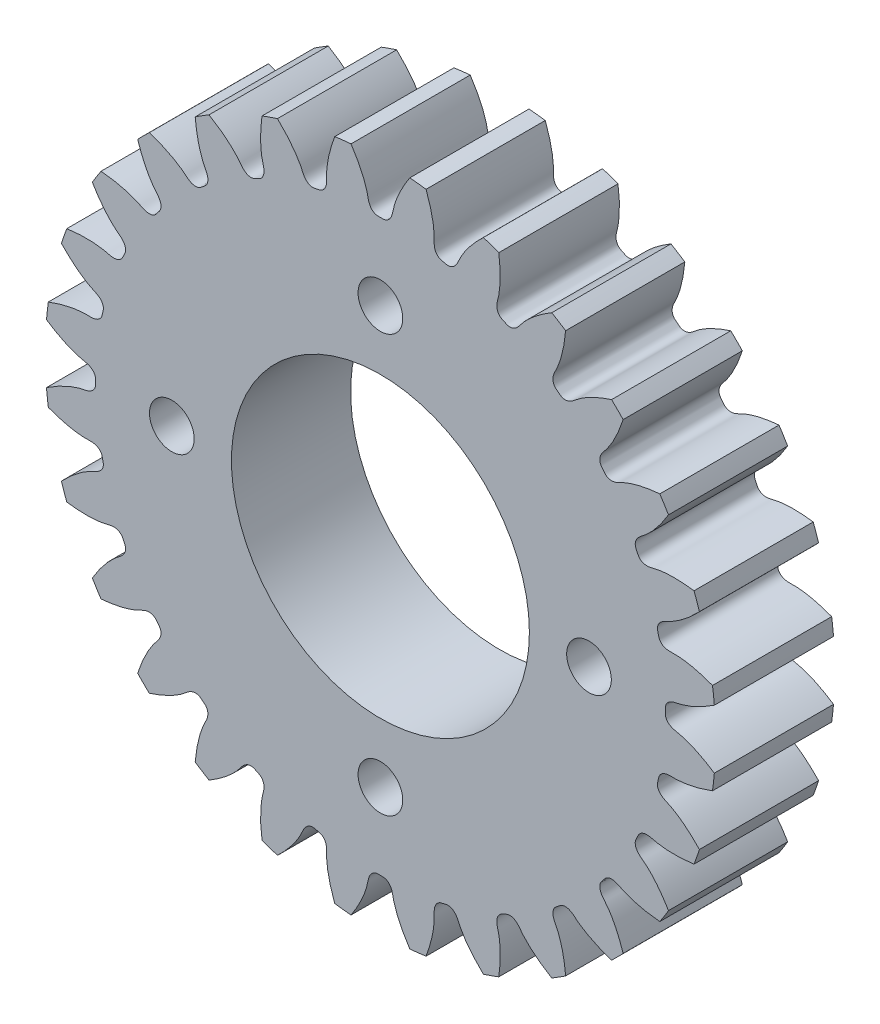
SolidWorks part; units mm, degrees
ref_plane "Front Plane" through (0, 0, 0) normal (0, 0, 1) x (1, 0, 0)
ref_plane "Top Plane" through (0, 0, 0) normal (0, 1, 0) x (1, 0, 0)
ref_plane "Right Plane" through (0, 0, 0) normal (1, 0, 0) x (0, 0, -1)
ref_axis "Axis1" through (0, 0, 4.4) along (0, 0, -1)
sketch "SketchRevolveSpurAssembly01Gear" plane through (0, 0, 0) normal (1, 0, 0) x (0, 0, -1)
  line L0 (0, 0) -> (1, 0) construction
  line L1 (-4, 0) -> (-4, 22.5)
  line L2 (-4, 22.5) -> (4, 22.5)
  line L3 (4, 22.5) -> (4, 0)
  line L4 (4, 0) -> (-4, 0)
  dimension "Side1" = 4
  dimension "OutsideRadius" = 22.5
  dimension "Side2" = 4
revolve "SpurAssembly01Gear" add sketch "SketchRevolveSpurAssembly01Gear" angle 360 about L0
sketch "SketchToothSpurAssembly01Gear" plane through (0, 0, 0) normal (0, 0, 1) x (1, 0, 0)
  arc A0 (22.4843, 2.0215) -> (22.4843, -2.0215) centre (0, 0) cw
  spline S0 degree 3 poles (22.4843, -2.0215) (22.4428, -1.9934) (22.3807, -1.9518) (22.2979, -1.8976) (22.2367, -1.8581) (22.176, -1.8196) (22.1159, -1.782) (22.0563, -1.7454) (21.9973, -1.7096) (21.9388, -1.6747) (21.881, -1.6408) (21.8237, -1.6077) (21.767, -1.5754) (21.7109, -1.5441) (21.6555, -1.5136) (21.6006, -1.4839) (21.5464, -1.455) (21.4929, -1.427) (21.44, -1.3998) (21.3877, -1.3733) (21.3362, -1.3477) (21.2853, -1.3228) (21.2351, -1.2987) (21.1856, -1.2754) (21.1368, -1.2528) (21.0887, -1.2309) (21.0413, -1.2098) (20.9947, -1.1894) (20.9487, -1.1696) (20.9036, -1.1506) (20.8592, -1.1322) (20.8155, -1.1145) (20.7726, -1.0975) (20.7304, -1.0811) (20.6891, -1.0653) (20.6485, -1.0502) (20.6087, -1.0356) (20.5697, -1.0217) (20.5315, -1.0084) (20.4942, -0.9956) (20.4576, -0.9834) (20.4219, -0.9717) (20.3869, -0.9606) (20.3529, -0.9499) (20.3196, -0.9399) (20.2872, -0.9303) (20.2557, -0.9212) (20.225, -0.9125) (20.1951, -0.9044) (20.1661, -0.8967) (20.138, -0.8894) (20.1108, -0.8825) (20.0844, -0.8761) (20.059, -0.8701) (20.0344, -0.8645) (20.0107, -0.8592) (19.9879, -0.8543) (19.966, -0.8498) (19.945, -0.8456) (19.9249, -0.8417) (19.8723, -0.832) (19.8119, -0.8212) (19.7446, -0.8048) (19.7028, -0.7934) (19.6619, -0.781) (19.6219, -0.7675) (19.5826, -0.7526) (19.544, -0.7364) (19.506, -0.7187) (19.4683, -0.699) (19.431, -0.6773) (19.394, -0.6531) (19.3572, -0.6258) (19.3207, -0.5949) (19.2846, -0.5597) (19.2494, -0.5194) (19.2159, -0.4733) (19.1851, -0.4207) (19.1587, -0.3613) (19.1384, -0.2957) (19.127, -0.2292) (19.1221, -0.13) (19.1271, 0) (19.1221, 0.13) (19.127, 0.2292) (19.1384, 0.2957) (19.1587, 0.3613) (19.1851, 0.4207) (19.2159, 0.4733) (19.2494, 0.5194) (19.2846, 0.5597) (19.3207, 0.5949) (19.3572, 0.6258) (19.394, 0.6531) (19.431, 0.6773) (19.4683, 0.699) (19.506, 0.7187) (19.544, 0.7364) (19.5826, 0.7526) (19.6219, 0.7675) (19.6619, 0.781) (19.7028, 0.7934) (19.7446, 0.8048) (19.8119, 0.8212) (19.8723, 0.832) (19.9249, 0.8417) (19.945, 0.8456) (19.966, 0.8498) (19.9879, 0.8543) (20.0107, 0.8592) (20.0344, 0.8645) (20.059, 0.8701) (20.0844, 0.8761) (20.1108, 0.8825) (20.138, 0.8894) (20.1661, 0.8967) (20.1951, 0.9044) (20.225, 0.9125) (20.2557, 0.9212) (20.2872, 0.9303) (20.3196, 0.9399) (20.3529, 0.9499) (20.3869, 0.9606) (20.4219, 0.9717) (20.4576, 0.9834) (20.4942, 0.9956) (20.5315, 1.0084) (20.5697, 1.0217) (20.6087, 1.0356) (20.6485, 1.0502) (20.6891, 1.0653) (20.7304, 1.0811) (20.7726, 1.0975) (20.8155, 1.1145) (20.8592, 1.1322) (20.9036, 1.1506) (20.9487, 1.1696) (20.9947, 1.1894) (21.0413, 1.2098) (21.0887, 1.2309) (21.1368, 1.2528) (21.1856, 1.2754) (21.2351, 1.2987) (21.2853, 1.3228) (21.3362, 1.3477) (21.3877, 1.3733) (21.44, 1.3998) (21.4929, 1.427) (21.5464, 1.455) (21.6006, 1.4839) (21.6555, 1.5136) (21.7109, 1.5441) (21.767, 1.5754) (21.8237, 1.6077) (21.881, 1.6408) (21.9388, 1.6747) (21.9973, 1.7096) (22.0563, 1.7454) (22.1159, 1.782) (22.176, 1.8196) (22.2367, 1.8581) (22.2979, 1.8976) (22.3807, 1.9518) (22.4428, 1.9934) (22.4843, 2.0215) knots 0 0 0 0 0.018126 0.027017 0.035793 0.044454 0.053001 0.061433 0.06975 0.077953 0.08604 0.094013 0.101872 0.109615 0.117244 0.124759 0.132158 0.139443 0.146613 0.153668 0.160609 0.167435 0.174146 0.180742 0.187224 0.193591 0.199843 0.205981 0.212003 0.217912 0.223705 0.229384 0.234948 0.240397 0.245731 0.250951 0.256056 0.261047 0.265922 0.270683 0.275329 0.279861 0.284277 0.288579 0.292767 0.296839 0.300797 0.30464 0.308369 0.311982 0.315481 0.318866 0.322135 0.32529 0.32833 0.331255 0.334066 0.336762 0.339343 0.34181 0.344162 0.358685 0.363984 0.369197 0.374338 0.379423 0.384472 0.389509 0.39456 0.399659 0.404844 0.410159 0.415656 0.421394 0.427439 0.433855 0.440707 0.448038 0.455865 0.464152 0.472805 0.480182 0.5 0.519818 0.527195 0.535848 0.544135 0.551962 0.559293 0.566145 0.572561 0.578606 0.584344 0.589841 0.595156 0.600341 0.60544 0.610491 0.615528 0.620577 0.625662 0.630803 0.636016 0.641315 0.655838 0.65819 0.660657 0.663238 0.665934 0.668745 0.67167 0.67471 0.677865 0.681134 0.684519 0.688018 0.691631 0.69536 0.699203 0.703161 0.707233 0.711421 0.715723 0.720139 0.724671 0.729317 0.734078 0.738953 0.743944 0.749049 0.754269 0.759603 0.765052 0.770616 0.776295 0.782088 0.787997 0.794019 0.800157 0.806409 0.812776 0.819258 0.825854 0.832565 0.839391 0.846332 0.853387 0.860557 0.867842 0.875241 0.882756 0.890385 0.898128 0.905987 0.91396 0.922047 0.93025 0.938567 0.946999 0.955546 0.964207 0.972983 0.981874 1 1 1 1
extrude "ToothExtrudeCutSpurAssembly01Gear" cut sketch "SketchToothSpurAssembly01Gear" against normal blind 4 and the other way blind 4
pattern_circular "PatternSpurAssembly01Gear" count 28 over 360 about axis through (0, 0, 4.4) along (0, 0, -1) of "ToothExtrudeCutSpurAssembly01Gear"
sketch "BoreRevolveSketch" plane through (0, 0, 0) normal (1, 0, 0) x (0, 0, -1)
  line L0 (0, 0) -> (1, 0) construction
  line L1 (-4, 0) -> (4, 0)
  line L2 (4, 0) -> (4, 10)
  line L3 (4, 10) -> (-4, 10)
  line L4 (-4, 10) -> (-4, 0)
  dimension "BoreSide1" = 4
  dimension "TaperSide1" = 10
  dimension "BoreSide2" = 4
  dimension "TaperSide2" = 10
revolve "BoreRevolveCut" cut sketch "BoreRevolveSketch" angle 360 about L0
sketch "AuxiliarySketchSpurAssembly01Gear" plane through (0, 0, 0) normal (0, 0, 1) x (1, 0, 0)
  circle A0 centre (0, 0) radius 21 construction
  circle A1 centre (0, 0) radius 19.7335 construction
  circle A2 centre (0, 0) radius 19.8997 construction
  circle A3 centre (0, 0) radius 22.5 construction
  circle A4 centre (0, 0) radius 19.125 construction
  dimension "PitchDiameter" = 42
  dimension "BaseDiameter" = 39.4671
  dimension "FormDiameter" = 39.7994
  dimension "MajorDiameter" = 45
  dimension "MinorDiameter" = 38.25
sketch "Sketch1" plane through (0, 0, 4) normal (0, 0, 1) x (1, 0, 0)
  circle A0 centre (-14, 0) radius 1.5
  dimension "D1" = 3
  dimension "D2" = 14
extrude "Cut-Extrude1" cut sketch "Sketch1" against normal through all
pattern_circular "CirPattern1" count 4 over 360 about axis through (0, 0, 0) along (0, 0, 1) of "Cut-Extrude1"
